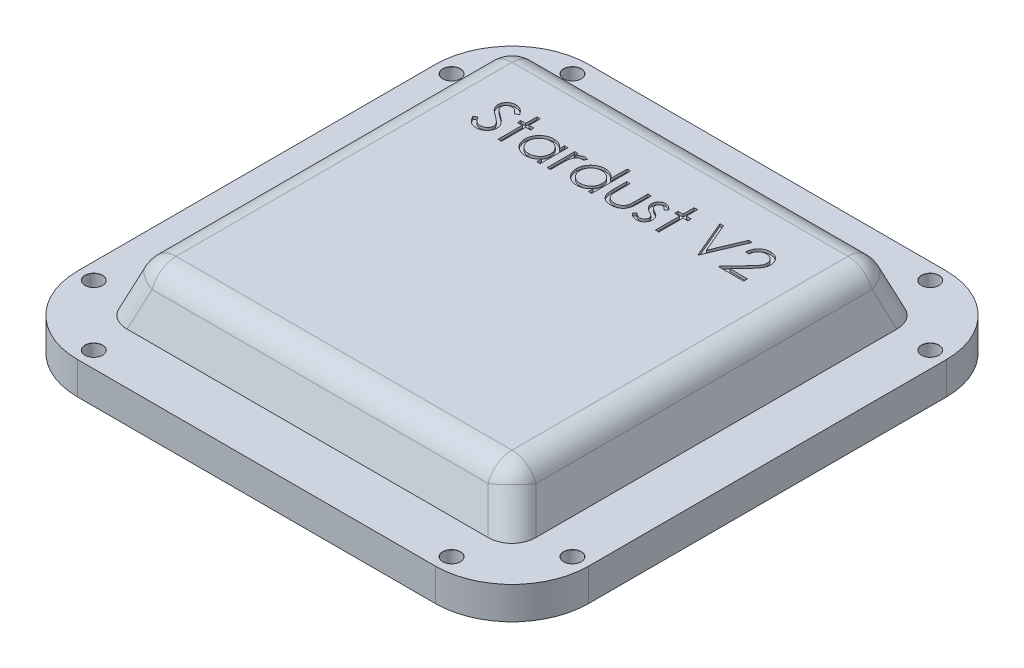
SolidWorks part; units mm, degrees
note: The reader was unsure of these and kept them because the rebuilt part matched: shared geometry of "Sketch4<2>".
material "ABS"
ref_plane "Front Plane" through (0, 0, 0) normal (0, 0, 1) x (1, 0, 0)
ref_plane "Top Plane" through (0, 0, 0) normal (0, 1, 0) x (1, 0, 0)
ref_plane "Right Plane" through (0, 0, 0) normal (1, 0, 0) x (0, 0, -1)
sketch "Sketch1" plane through (0, 0, 0) normal (0, 1, 0) x (1, 0, 0)
  line L1 (-50, -50) -> (50, -50)
  line L2 (-50, -50) -> (-50, 50)
  line L3 (-50, 50) -> (50, 50)
  line L4 (50, -50) -> (50, 50)
  line L5 (-50, -50) -> (50, 50) construction
  line L6 (-50, 50) -> (50, -50) construction
  line L7 (-50, 46.825) -> (-33, 46.825)
  line L9 (-46.825, 50) -> (-46.825, 33)
  line L10 (-50, 0) -> (50, 0)
  point P1 (0, 0)
  point P10 (46.825, -33)
  point P11 (33, -46.825)
  point P14 (46.825, 33)
  point P15 (33, 46.825)
  point P16 (-33, -46.825)
  point P17 (-46.825, -33)
extrude "Boss-Extrude1" add sketch "Sketch1" along normal blind 6.35
hole_wizard "M3 Clearance Hole1" positions "Sketch2" profile "Sketch3" hole size "M3" standard "ANSI Metric" end condition through all
sketch "Sketch2" plane through (0, 6.35, 0) normal (0, 1, 0) x (1, 0, 0)
  line L0 (-50, -50) -> (-35, -50)
  line L1 (-50, -50) -> (50, -50) construction
  line L2 (-35, -50) -> (-35, -46.825)
  line L4 (-50, -50) -> (-50, -35)
  line L5 (-50, -50) -> (-50, 50) construction
  line L6 (-50, -35) -> (-46.825, -35)
  line L9 (-50, 50) -> (50, -50)
  line L11 (-50, 0) -> (50, 0)
  line L12 (50, -50) -> (50, 50) construction
  line L14 (50, 50) -> (-50, -50)
  point P67 (46.825, 35)
  point P68 (35, 46.825)
  point P69 (46.825, -35)
  point P70 (35, -46.825)
  point P71 (-46.825, 35)
  point P72 (-35, 46.825)
sketch "Sketch3" plane through (-35, 6.35, -46.825) normal (1, 0, 0) x (0, 0, 1)
  line L0 (0, 0) -> (0, 6.35)
  line L1 (0, 6.35) -> (1.7, 6.35)
  line L2 (1.7, 6.35) -> (1.7, 0.025)
  line L3 (1.7, 0.025) -> (1.725, 0)
  line L5 (1.725, 0) -> (0, 0)
  line L6 (-1.7, 0.025) -> (-1.725, 0) construction
  line L11 (0, -6.35) -> (0, 107.95) construction
  dimension "Thru Hole Dia." = 3.4
  dimension "Thru Hole Depth" = 6.35
  dimension "Near C'Sink Dia." = 3.45
  dimension "Near C'Sink Angle" = 90
fillet "Fillet1" radius 15 4 edges at (-50, 3.175, -50) (50, 3.175, -50) (50, 3.175, 50) (-50, 3.175, 50)
sketch "Sketch4" plane through (0, 6.35, 0) normal (0, 1, 0) x (1, 0, 0)
  line L1 (40, -40) -> (-40, -40)
  line L2 (40, -40) -> (40, 40)
  line L3 (40, 40) -> (-40, 40)
  line L4 (-40, -40) -> (-40, 40)
  line L5 (40, -40) -> (-40, 40) construction
  line L6 (40, 40) -> (-40, -40) construction
  point P1 (0, 0)
extrude "Boss-Extrude3" add sketch "Sketch4" along normal blind 10
chamfer "Chamfer1" distance 10 angle 20 4 edges at (40, 16.35, 0) (0, 16.35, 40) (0, 16.35, -40) (-40, 16.35, 0) first distance on face at (40, 11.35, 0) first distance on face at (0, 11.35, 40) first distance on face at (0, 11.35, -40) first distance on face at (-40, 11.35, 0)
fillet "Fillet4" radius 5 4 edges at (0, 16.35, -36.3603) (36.3603, 16.35, 0) (0, 16.35, 36.3603) (-36.3603, 16.35, 0)
fillet "Fillet5" radius 5 8 edges at (-35.7271, 15.4458, 35.7271) (-35.7271, 15.4458, -35.7271) (35.7271, 15.4458, -35.7271) (35.7271, 15.4458, 35.7271) (-38.7789, 9.7051, 38.7789) (-38.7789, 9.7051, -38.7789) (38.7789, 9.7051, -38.7789) (38.7789, 9.7051, 38.7789)
sketch "Sketch5" plane through (0, 16.35, 0) normal (0, 1, 0) x (1, 0, 0)
  text T0 "Stardust V2" font "Century Gothic" height in points 28
extrude "Cut-Extrude1" cut sketch "Sketch5" against normal blind 0.5
hole_wizard "M3 Clearance Hole2" positions "Sketch6" profile "Sketch7" hole size "M3" standard "ANSI Metric" end condition through all
sketch "Sketch6" plane through (0, 6.35, 0) normal (0, 1, 0) x (1, 0, 0)
  point P0 (-46.825, -35)
  point P3 (-35, -46.825)
sketch "Sketch7" plane through (-46.825, 6.35, 35) normal (1, 0, 0) x (0, 0, 1)
  line L0 (0, 0) -> (0, 6.35)
  line L1 (0, 6.35) -> (1.7, 6.35)
  line L2 (1.7, 6.35) -> (1.7, 0.025)
  line L3 (1.7, 0.025) -> (1.725, 0)
  line L5 (1.725, 0) -> (0, 0)
  line L6 (-1.7, 0.025) -> (-1.725, 0) construction
  line L11 (0, -6.35) -> (0, 107.95) construction
  dimension "Thru Hole Dia." = 3.4
  dimension "Thru Hole Depth" = 6.35
  dimension "Near C'Sink Dia." = 3.45
  dimension "Near C'Sink Angle" = 90
extrude "Cut-Extrude2" cut sketch "Sketch4<2>" against normal blind 23.5 contours L1 L4 L3 L2
sketch "Sketch4<2>" plane through (0, 6.35, 0) normal (0, 1, 0) x (1, 0, 0) same geometry as "Sketch4"
fillet "Fillet6" radius 15 4 edges at (-40, 3.175, -40) (-40, 3.175, 40) (40, 3.175, 40) (40, 3.175, -40)
sketch "Sketch8" plane through (0, 6.35, 0) normal (0, -1, 0) x (1, 0, 0)
  line L1 (-32.86, -32.86) -> (32.86, -32.86)
  line L2 (-32.86, -32.86) -> (-32.86, 32.86)
  line L3 (-32.86, 32.86) -> (32.86, 32.86)
  line L4 (32.86, -32.86) -> (32.86, 32.86)
  line L5 (-32.86, -32.86) -> (32.86, 32.86) construction
  line L6 (-32.86, 32.86) -> (32.86, -32.86) construction
  point P0 (0, 0)
extrude "Cut-Extrude3" cut sketch "Sketch8" against normal offset from surface (7 mm away) 3 up to face at (-10.5066, 16.35, -22.307)
fillet "Fillet7" radius 3 4 edges at (0, 6.35, -32.86) (32.86, 6.35, 0) (-32.86, 6.35, 0) (0, 6.35, 32.86)
